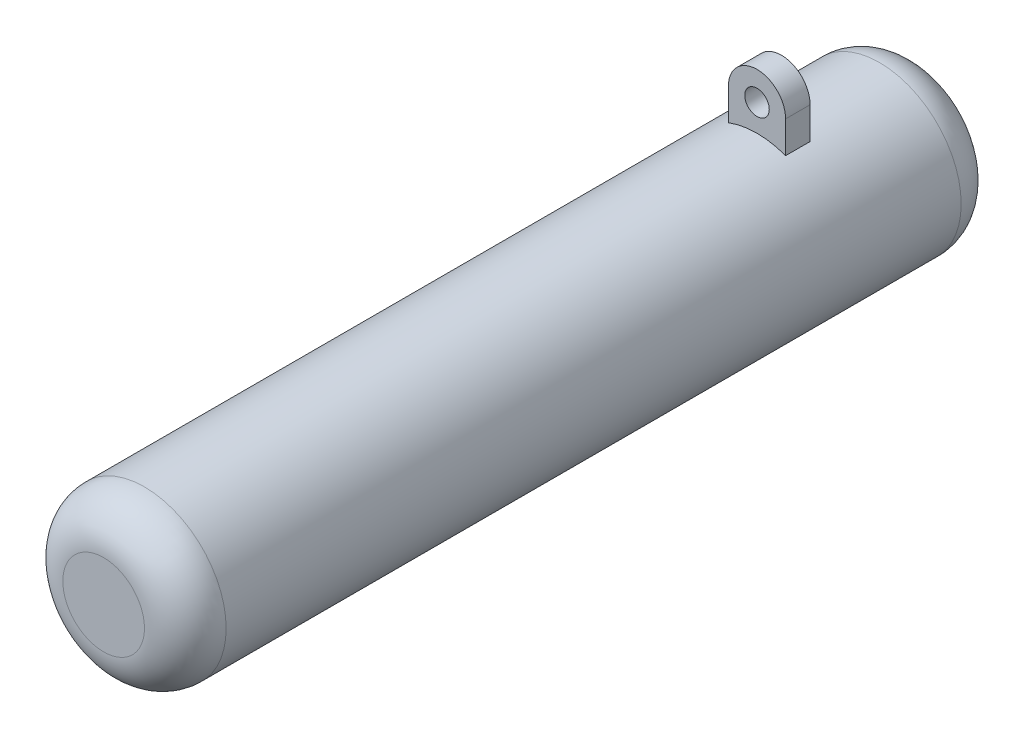
SolidWorks part; units mm, degrees
ref_plane "Front Plane" through (0, 0, 0) normal (0, 0, 1) x (1, 0, 0)
ref_plane "Top Plane" through (0, 0, 0) normal (0, 1, 0) x (1, 0, 0)
ref_plane "Right Plane" through (0, 0, 0) normal (1, 0, 0) x (0, 0, -1)
sketch "Sketch1" plane through (0, 0, 0) normal (0, 0, 1) x (1, 0, 0)
  circle A0 centre (0, 0) radius 10
  point P3 (0, 0)
  dimension "D1" = 20
extrude "Boss-Extrude1" add sketch "Sketch1" along normal blind 100
fillet "Fillet1" radius 5 2 edges at (10, 0, 0) (10, 0, 100)
ref_plane "Plane1" through (0, 0, 20) normal (0, 0, 1) x (1, 0, 0)
sketch "Sketch2" plane through (0, 0, 20) normal (0, 0, 1) x (1, 0, 0)
  line L2 (3.5, 9.3675) -> (3.5, 13.2702)
  line L4 (-3.5, 9.3675) -> (-3.5, 13.2702)
  circle A0 centre (0, 0) radius 10 construction
  arc A1 (-3.5, 13.2702) -> (3.5, 13.2702) centre (0, 13.2702) cw
  arc A2 (-3.5, 9.3675) -> (3.5, 9.3675) centre (0, 0) cw
  circle A3 centre (0, 13.2702) radius 1.5
  point P0 (0, 10)
  dimension "D2" = 3
  dimension "D1" = 7
extrude "Boss-Extrude2" add sketch "Sketch2" against normal blind 3 separate body
ref_axis "Axis2" through (0, 13.2702, 17) along (0, 0, 1)
